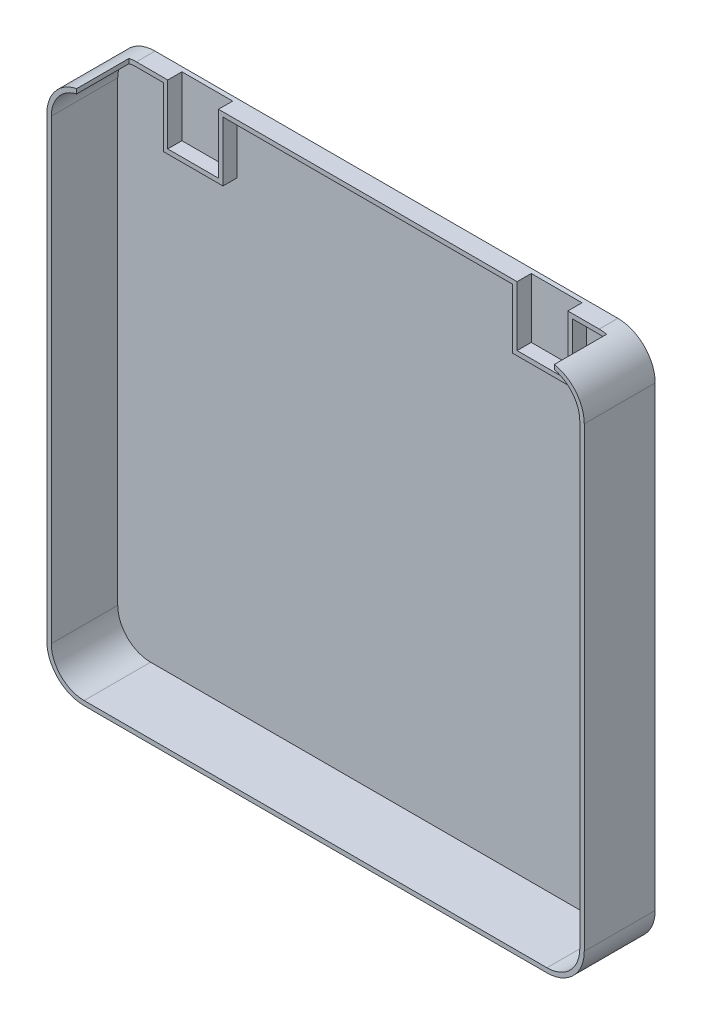
SolidWorks part; units mm, degrees
ref_plane "Plan de face" through (0, 0, 0) normal (0, 0, 1) x (1, 0, 0)
ref_plane "Plan de dessus" through (0, 0, 0) normal (0, 1, 0) x (1, 0, 0)
ref_plane "Plan de droite" through (0, 0, 0) normal (1, 0, 0) x (0, 0, -1)
sketch "Esquisse1" plane through (0, 0, 0) normal (0, 0, 1) x (1, 0, 0)
  line L1 (0, 0) -> (360, 0)
  line L2 (0, 0) -> (0, 356)
  line L3 (0, 356) -> (360, 356)
  line L4 (360, 0) -> (360, 356)
  dimension "D1" = 360
  dimension "D2" = 356
extrude "Boss.-Extru.1" add sketch "Esquisse1" along normal blind 47.5
fillet "Congé1" radius 25 4 edges at (0, 0, 23.75) (360, 0, 23.75) (360, 356, 23.75) (0, 356, 23.75)
sketch "Esquisse2" plane through (0, 0, 47.5) normal (0, 0, 1) x (1, 0, 0)
  line L8 (3, 331) -> (3, 25)
  line L9 (25, 3) -> (335, 3)
  line L10 (357, 25) -> (357, 331)
  line L11 (335, 353) -> (25, 353)
  line L12 (3, 331) -> (3, 25)
  line L13 (25, 3) -> (335, 3)
  line L14 (357, 25) -> (357, 331)
  line L15 (335, 353) -> (25, 353)
  arc A8 (3, 25) -> (25, 3) centre (25, 25) ccw
  arc A9 (335, 3) -> (357, 25) centre (335, 25) ccw
  arc A10 (357, 331) -> (335, 353) centre (335, 331) ccw
  arc A11 (25, 353) -> (3, 331) centre (25, 331) ccw
  arc A12 (3, 25) -> (25, 3) centre (25, 25) ccw
  arc A13 (335, 3) -> (357, 25) centre (335, 25) ccw
  arc A14 (357, 331) -> (335, 353) centre (335, 331) ccw
  arc A15 (25, 353) -> (3, 331) centre (25, 331) ccw
  dimension "D1" = 3
extrude "Enlèv. mat.-Extru.1" cut sketch "Esquisse2" against normal blind 44.5 contours L12 A12 L13 A13 L14 A14 L15 A15
sketch "Esquisse3" plane through (0, 356, 0) normal (0, 1, 0) x (1, 0, 0)
  line L0 (335, -47.5) -> (25, -47.5) construction
  line L1 (20, -47.5) -> (340, -47.5)
  line L2 (20, -47.5) -> (20, -12.5)
  line L3 (20, -12.5) -> (340, -12.5)
  line L4 (340, -47.5) -> (340, -12.5)
  line L5 (0, -47.5) -> (0, 0) construction
  dimension "D1" = 35
  dimension "D2" = 320
  dimension "D3" = 20
extrude "Enlèv. mat.-Extru.2" cut sketch "Esquisse3" against normal blind 10 contours L2 L1 L4 L3
sketch "Esquisse4" plane through (0, 3, 0) normal (0, 1, 0) x (1, 0, 0)
  line L0 (180, 0) -> (180, -47.5) construction
  line L1 (335, 0) -> (25, 0) construction
  line L2 (25, -47.5) -> (335, -47.5) construction
sketch "Esquisse5" plane through (0, 0, 3) normal (0, 0, 1) x (1, 0, 0)
  line L0 (180, 99.9998) -> (180, 353) construction
  line L1 (25, 353) -> (335, 353) construction
  line L2 (335, 353) -> (25, 353) construction
  line L3 (43, 353) -> (83, 353)
  line L4 (43, 353) -> (43, 313)
  line L5 (43, 313) -> (83, 313)
  line L6 (83, 353) -> (83, 313)
  line L7 (3, 331) -> (3, 25) construction
  line L8 (317, 313) -> (277, 313)
  line L9 (277, 353) -> (277, 313)
  line L10 (317, 353) -> (277, 353)
  line L11 (317, 353) -> (317, 313)
  point P6 (180, 353)
  line M17 (335, 353) -> (25, 353)
  dimension "D1" = 40
  dimension "D2" = 40
  dimension "D3" = 40
extrude "Extru.-Mince1" add sketch "Esquisse5" along normal blind 9.5 thin contours L6 L4 L5 M17 | L8 L9 L10 L11 thin type one direction reverse wall 3
sketch "Esquisse9" plane through (0, 0, 12.5) normal (0, 0, 1) x (1, 0, 0)
  line L0 (314, 350) -> (314, 356) construction
  line L1 (25, 356) -> (335, 356) construction
  line L2 (280, 350) -> (280, 356) construction
sketch "Esquisse10" plane through (0, 356, 0) normal (0, 1, 0) x (1, 0, 0)
  line L0 (25, -12.5) -> (335, -12.5) construction
  line L1 (280, -12.5) -> (314, -12.5)
  line L2 (280, -12.5) -> (280, -3)
  line L3 (280, -3) -> (314, -3)
  line L4 (314, -12.5) -> (314, -3)
  dimension "D1" = 9.5
  dimension "D2" = 34
  dimension "D3" = 0
extrude "Enlèv. mat.-Extru.4" cut sketch "Esquisse10" against normal blind 10 contours L2 L1 L4 L3
sketch "Esquisse12" plane through (0, 0, 12.5) normal (0, 0, 1) x (1, 0, 0)
  line L0 (46, 350) -> (46, 356) construction
  line L1 (25, 356) -> (280, 356) construction
  line L2 (80, 350) -> (80, 356) construction
sketch "Esquisse13" plane through (0, 356, 0) normal (0, 1, 0) x (1, 0, 0)
  line L0 (25, -12.5) -> (280, -12.5) construction
  line L1 (46, -12.5) -> (80, -12.5)
  line L2 (46, -12.5) -> (46, -3)
  line L3 (46, -3) -> (80, -3)
  line L4 (80, -12.5) -> (80, -3)
  dimension "D1" = 34
  dimension "D2" = 9.5
  dimension "D3" = 0
  dimension "D4" = 0
extrude "Enlèv. mat.-Extru.5" cut sketch "Esquisse13" against normal blind 10
